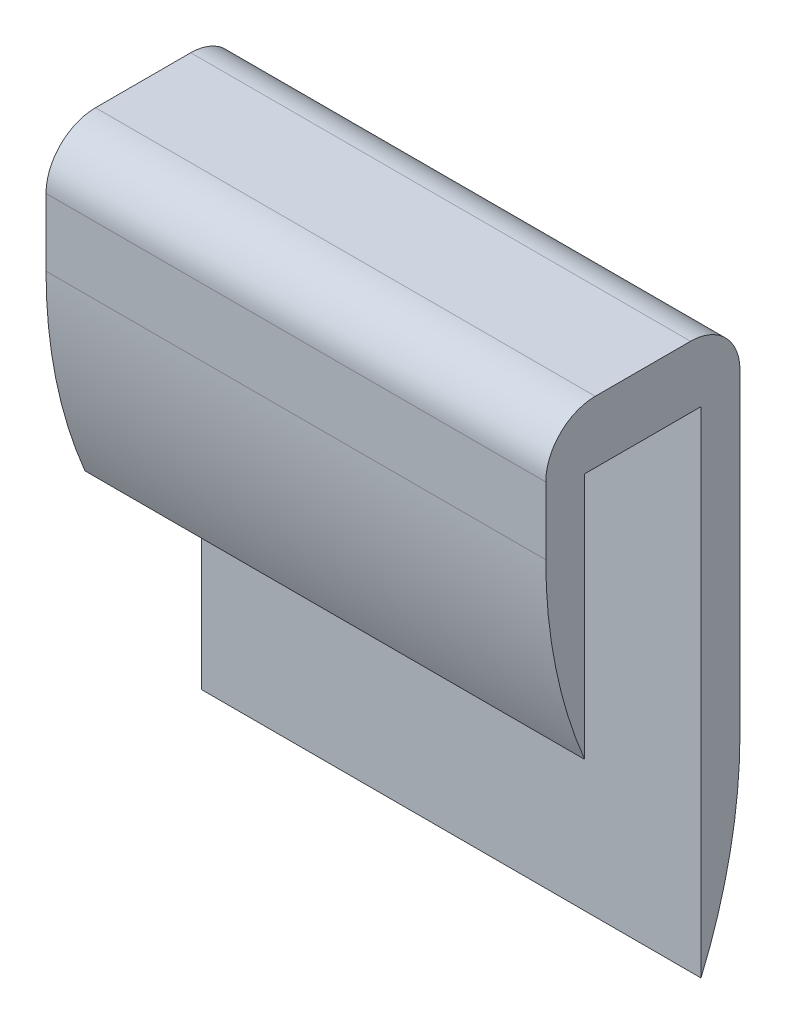
SolidWorks part; units mm, degrees
ref_plane "Front Plane" through (0, 0, 0) normal (0, 0, 1) x (1, 0, 0)
ref_plane "Top Plane" through (0, 0, 0) normal (0, 1, 0) x (1, 0, 0)
ref_plane "Right Plane" through (0, 0, 0) normal (1, 0, 0) x (0, 0, -1)
sketch "Sketch1" plane through (0, 0, 0) normal (1, 0, 0) x (0, 0, -1)
  line L0 (-4.9845, -12.7) -> (-2.9845, -12.7)
  line L1 (-2.9845, -12.7) -> (-2.9845, 0)
  line L2 (-2.9845, 0) -> (2.9845, 0)
  line L3 (2.9845, 0) -> (2.9845, -25.4)
  line L4 (2.9845, -25.4) -> (4.9845, -25.4)
  line L5 (4.9845, -25.4) -> (4.9845, 3.175)
  line L6 (4.9845, 3.175) -> (-4.9845, 3.175)
  line L7 (-4.9845, 3.175) -> (-4.9845, -12.7)
  point P6 (0, 0)
  dimension "D1" = 2
  dimension "D2" = 12.7
  dimension "D3" = 3.175
  dimension "D4" = 5.969
  dimension "D5" = 25.4
extrude "Boss-Extrude1" add sketch "Sketch1" along normal blind 25.654
fillet "Fillet1" radius 25.4 2 edges at (12.827, -12.7, 4.9845) (12.827, -25.4, -4.9845)
fillet "Fillet2" radius 2.54 2 edges at (12.827, 3.175, -4.9845) (12.827, 3.175, 4.9845)
equation "\"Height\"= 12in"
equation "\"Depth\"= 7in"
equation "\"WallThickness\"= 0.125in"
equation "\"FloorThickness\"= 0.25in"
equation "\"Width\" = 30in"
equation "\"D4@Sketch1\"=\"WallThickness\"*2-.015"
